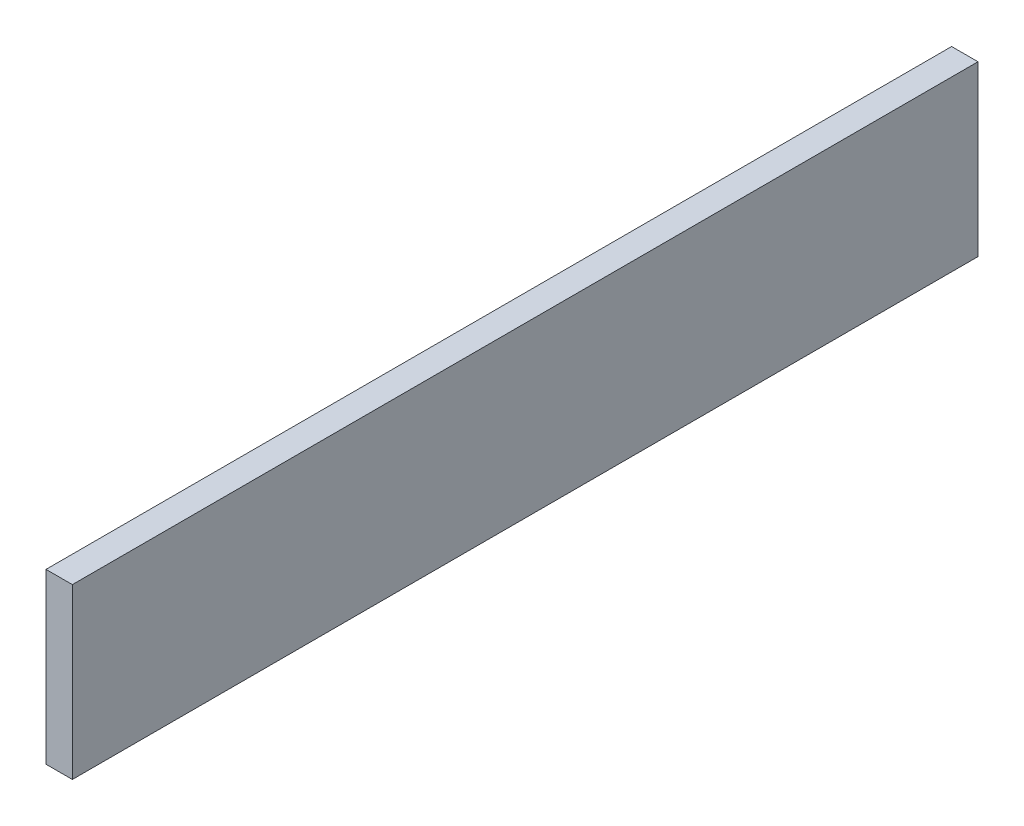
SolidWorks part; units mm, degrees
ref_plane "Front Plane" through (0, 0, 0) normal (1, 0, 0) x (0, 1, 0)
ref_plane "Top Plane" through (0, 0, 0) normal (0, 0, 1) x (0, 1, 0)
ref_plane "Right Plane" through (0, 0, 0) normal (0, 1, 0) x (-1, 0, 0)
sketch "Sketch1" plane through (0, 0, 0) normal (1, 0, 0) x (0, 1, 0)
  line L0 (-768.1, 3162.3) -> (-768.1, 3048.381)
  line L1 (-768.1, 3048.381) -> (-791.0195, 3048.381)
  line L3 (-800.1, 3048.381) -> (-800.1, 2990.596)
  line L4 (-800.1, 2990.596) -> (-768.1, 2990.596)
  line L5 (-768.1, 2990.596) -> (-768.1, 3048.381)
  line L14 (-804.2275, 2990.596) -> (-804.2275, 2922.905)
  line L15 (-804.2275, 2922.905) -> (-691.9595, 2922.905)
  line L16 (-691.9595, 2922.905) -> (-691.9595, 2990.596)
  line L17 (-691.9595, 2990.596) -> (-705.1675, 2990.596)
  line L18 (-705.1675, 2990.596) -> (-705.1675, 3048.381)
  line L19 (-705.1675, 3048.381) -> (-696.087, 3048.381)
  line L20 (-696.087, 3048.381) -> (-696.087, 3092.958)
  line L21 (-696.087, 3092.958) -> (-701.04, 3092.958)
  line L22 (-701.04, 3092.958) -> (-701.04, 3162.3)
  line L23 (-701.04, 3162.3) -> (-800.1, 3162.3)
  line L24 (-800.1, 3162.3) -> (-800.1, 3048.381)
  line L25 (-800.1, 3048.381) -> (-791.0195, 3048.381)
  line L26 (-791.0195, 3048.381) -> (-791.0195, 2990.596)
  line L27 (-791.0195, 2990.596) -> (-804.2275, 2990.596)
  line L28 (-804.2275, 2990.596) -> (-804.2275, 2922.905)
  line L29 (-804.2275, 2922.905) -> (-691.9595, 2922.905)
  line L30 (-691.9595, 2922.905) -> (-691.9595, 2990.596)
  line L31 (-691.9595, 2990.596) -> (-705.1675, 2990.596)
  line L32 (-705.1675, 2990.596) -> (-705.1675, 3048.381)
  line L33 (-705.1675, 3048.381) -> (-696.087, 3048.381)
  line L34 (-696.087, 3048.381) -> (-696.087, 3092.958)
  line L35 (-696.087, 3092.958) -> (-701.04, 3092.958)
  line L36 (-701.04, 3092.958) -> (-701.04, 3162.3)
  line L37 (-701.04, 3162.3) -> (-800.1, 3162.3)
  line L38 (-800.1, 3162.3) -> (-800.1, 3048.381)
  line L39 (-800.1, 3048.381) -> (-791.0195, 3048.381)
  line L40 (-791.0195, 3048.381) -> (-791.0195, 2990.596)
  line L41 (-791.0195, 2990.596) -> (-804.2275, 2990.596)
  dimension "D2" = 32
  dimension "D1" = 0
extrude "Boss-Extrude1" add sketch "Sketch1" along normal blind 5 from offset 50 contours L38 L39 L1 L0 L37 | L1 L40 L4 L5 | L40 L39 L3 L4 region at (0, -784.1, 3105.3405) region at (0, -779.5598, 3019.4885) region at (0, -795.5598, 3019.4885)
